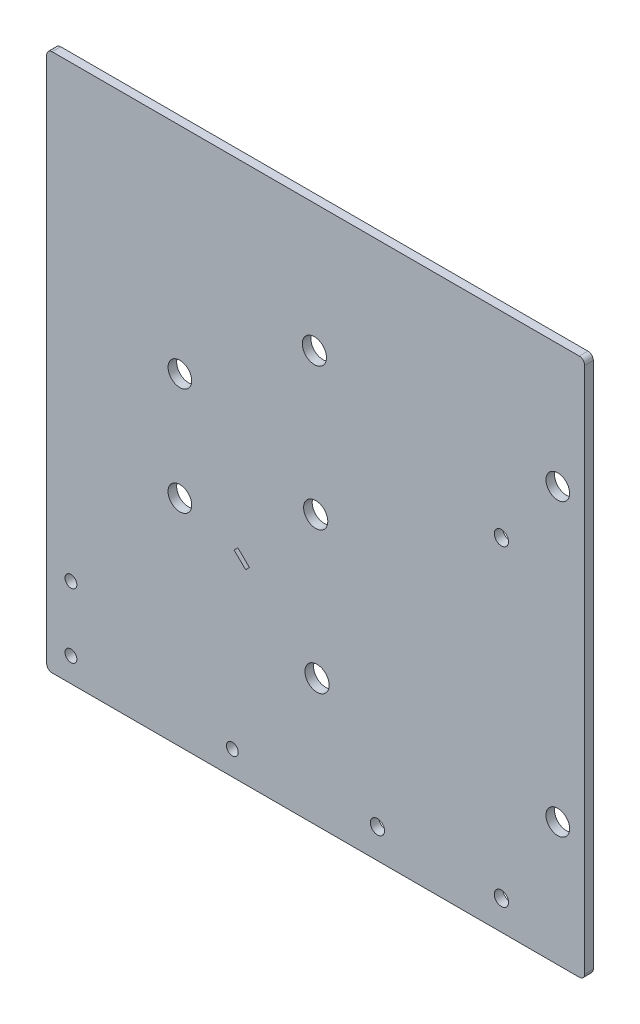
SolidWorks part; units mm, degrees
material "FR4_stuffedProtoboard"
ref_plane "Front Plane" through (0, 0, 0) normal (0, 0, 1) x (1, 0, 0)
ref_plane "Top Plane" through (0, 0, 0) normal (0, 1, 0) x (1, 0, 0)
ref_plane "Right Plane" through (0, 0, 0) normal (1, 0, 0) x (0, 0, -1)
sketch "Sketch1" plane through (0, 0, 0) normal (0, 0, 1) x (1, 0, 0)
  line L1 (-50, -50) -> (50, -50)
  line L2 (-50, -50) -> (-50, 50)
  line L3 (-50, 50) -> (50, 50)
  line L4 (50, -50) -> (50, 50)
  line L5 (-50, -50) -> (50, 50) construction
  line L6 (-50, 50) -> (50, -50) construction
  dimension "D1" = 100
extrude "Boss-Extrude1" add sketch "Sketch1" along normal blind 1.6
sketch "Sketch2" [suppressed] plane through (0, 0, 1.6) normal (0, 0, 1) x (1, 0, 0)
  circle A0 centre (0, 0) radius 50
  line M2 (50, -50) -> (50, 50)
  line M3 (50, 50) -> (-50, 50)
  line M4 (-50, 50) -> (-50, -50)
  line M5 (-50, -50) -> (50, -50)
  dimension "D1" = 100
extrude "Cut-Extrude1" [suppressed] cut sketch "Sketch2" against normal blind 1.6 contours A0 M3 M4 | A0 M4 M5 | A0 M5 M2 | A0 M2 M3
sketch "Sketch3" plane through (0, 0, 1.6) normal (0, 0, -1) x (-1, 0, 0)
  line L0 (-40, -22) -> (-50, -22) construction
  line L1 (-40, -32) -> (-40, -22) construction
  line L2 (-50, -32) -> (-40, -32) construction
  line L3 (-50, -22) -> (-50, -32) construction
  line L4 (-40, -22) -> (-50, -22)
  line L5 (-40, -32) -> (-40, -22)
  line L6 (-50, -32) -> (-40, -32)
  line L7 (-50, -22) -> (-50, -32)
  line L8 (-40, 22) -> (-40, 32) construction
  line L9 (-40, 32) -> (-50, 32) construction
  line L10 (-50, 32) -> (-50, 22) construction
  line L11 (-50, 22) -> (-40, 22) construction
  line L12 (-40, 22) -> (-40, 32)
  line L13 (-40, 32) -> (-50, 32)
  line L14 (-50, 32) -> (-50, 22)
  line L15 (-50, 22) -> (-40, 22)
  line L16 (5, -22) -> (-5, -22) construction
  line L17 (5, -32) -> (5, -22) construction
  line L18 (-5, -32) -> (5, -32) construction
  line L19 (-5, -22) -> (-5, -32) construction
  line L20 (5, -22) -> (-5, -22)
  line L21 (5, -32) -> (5, -22)
  line L22 (-5, -32) -> (5, -32)
  line L23 (-5, -22) -> (-5, -32)
  line L24 (5, 22) -> (5, 32) construction
  line L25 (5, 32) -> (-5, 32) construction
  line L26 (-5, 32) -> (-5, 22) construction
  line L27 (-5, 22) -> (5, 22) construction
  line L28 (5, 22) -> (5, 32)
  line L29 (5, 32) -> (-5, 32)
  line L30 (-5, 32) -> (-5, 22)
  line L31 (-5, 22) -> (5, 22)
  line L32 (17.2447, 25) -> (45.2447, 25) construction
  line L33 (45.2447, 25) -> (45.2447, -25) construction
  line L34 (17.2447, -25) -> (45.2447, -25) construction
  line L35 (17.2447, 25) -> (17.2447, -25) construction
  line L36 (17.2447, 25) -> (45.2447, 25)
  line L37 (45.2447, 25) -> (45.2447, -25)
  line L38 (17.2447, -25) -> (45.2447, -25)
  line L39 (17.2447, 25) -> (17.2447, -25)
  circle A0 centre (0.2447, 26.2506) radius 2.2479 construction
  circle A2 centre (0.2447, 26.2506) radius 2.2479
  circle A3 centre (0, 0) radius 2.2479
  circle A4 centre (-34.525, -44.525) radius 1.325 construction
  circle A6 centre (-34.525, -44.525) radius 1.325
  circle A8 centre (-0.2446, -26.2471) radius 2.2479 construction
  circle A9 centre (-0.2446, -26.2471) radius 2.2479
  circle A11 centre (-45, -27) radius 2.2
  circle A13 centre (-45, 27) radius 2.2
  circle A14 centre (-34.525, 13.525) radius 1.325 construction
  circle A15 centre (-34.525, 13.525) radius 1.325
  circle A16 centre (15.5, -45.5) radius 1.1 construction
  circle A17 centre (15.5, -45.5) radius 1.1
  circle A18 centre (45.5, -45.5) radius 1.1 construction
  circle A19 centre (45.5, -45.5) radius 1.1
  circle A20 centre (45.5, -33.5) radius 1.1 construction
  circle A21 centre (45.5, -33.5) radius 1.1
  circle A22 centre (-11.475, -44.525) radius 1.325 construction
  circle A23 centre (-11.475, -44.525) radius 1.325
  circle A24 centre (25.2447, -9.9994) radius 2.2 construction
  circle A25 centre (25.2447, -9.9994) radius 2.2
  circle A26 centre (25.2447, 10.0006) radius 2.2 construction
  circle A27 centre (25.2447, 10.0006) radius 2.2
  circle A28 centre (-45, 27) radius 2.2 construction
  circle A29 centre (-45, 27) radius 2.2
  circle A30 centre (-45, -27) radius 2.2 construction
  circle A31 centre (-45, -27) radius 2.2
  dimension "D1" = 4.4958
extrude "Cut-Extrude2" cut sketch "Sketch3" along normal through all contours A13 | A11 | A2 | A9 | A3 | A15 | A6 | A23 | A27 | A25 | A17 | A21 | A19 region at (-0.2447, 26.2506, 1.6) region at (0, 0, 1.6) region at (34.525, -44.525, 1.6) region at (0.2446, -26.2471, 1.6) region at (45, -27, 1.6) region at (45, 27, 1.6) region at (34.525, 13.525, 1.6) region at (-15.5, -45.5, 1.6) region at (-45.5, -45.5, 1.6) region at (-45.5, -33.5, 1.6) region at (11.475, -44.525, 1.6) region at (-25.2447, -9.9994, 1.6) region at (-25.2447, 10.0006, 1.6)
sketch "Sketch4" plane through (0, 0, 1.6) normal (0, 0, 1) x (1, 0, 0)
  line L0 (38, -44.25) -> (38, -18.925) construction
  line L5 (38, -44.25) -> (38, -18.925)
  line L6 (11.75, -48) -> (34.25, -48) construction
  line L7 (11.75, -48) -> (34.25, -48)
  line L8 (8, -44.25) -> (8, 13.25) construction
  line L9 (8, -44.25) -> (8, 13.25)
  line L11 (33, -3) -> (33, -48) construction
  line L13 (34.25, 17) -> (11.75, 17)
  line L14 (38, 13.25) -> (38, -18.925)
  line L15 (-48, -48) -> (-13, -48) construction
  line L16 (-48, -48) -> (-13, -48)
  line L17 (-48, -31) -> (-48, -48) construction
  line L18 (-48, -31) -> (-48, -48)
  line L19 (-13, -40.5) -> (-13, -32.5) construction
  line L20 (-13, -40.5) -> (-13, -32.5)
  line L21 (-13, -48) -> (-13, -40.5) construction
  line L22 (-13, -48) -> (-13, -40.5)
  line L23 (-13, -32.5) -> (-13, -31) construction
  line L24 (-13, -32.5) -> (-13, -31)
  line L25 (-13, -31) -> (-48, -31) construction
  line L26 (-13, -31) -> (-48, -31)
  line L27 (-20, -34) -> (-20, -48) construction
  arc A0 (34.25, -48) -> (38, -44.25) centre (34.25, -44.25) ccw construction
  arc A1 (34.25, -48) -> (38, -44.25) centre (34.25, -44.25) ccw
  arc A2 (8, -44.25) -> (11.75, -48) centre (11.75, -44.25) ccw construction
  arc A3 (8, -44.25) -> (11.75, -48) centre (11.75, -44.25) ccw
  arc A4 (11.75, 17) -> (8, 13.25) centre (11.75, 13.25) ccw construction
  arc A5 (11.75, 17) -> (8, 13.25) centre (11.75, 13.25) ccw
  arc A6 (38, 13.25) -> (34.25, 17) centre (34.25, 13.25) ccw construction
  arc A7 (38, 13.25) -> (34.25, 17) centre (34.25, 13.25) ccw
  text T0 "Raspberry Pi Zero W" font "Century Gothic" height 2
  text T1 "Atheros" font "Century Gothic" height 2
  dimension "D1" = 5
  dimension "D2" = 20
  dimension "D3" = 3
  dimension "D4" = 7
fillet "Fillet1" radius 1 4 edges at (-50, -50, 0.8) (-50, 50, 0.8) (50, -50, 0.8) (50, 50, 0.8)
sketch "Sketch5" plane through (0, 0, 0) normal (0, 0, -1) x (-1, 0, 0)
  line L0 (-10.2815, -30.1538) -> (-10.1686, -18.0444) construction
  line L5 (9.8305, -18.2308) -> (9.7177, -30.3402) construction
  line L6 (-10.2815, -30.1538) -> (-10.1686, -18.0444)
  line L7 (9.8305, -18.2308) -> (9.7177, -30.3402)
  line L8 (-9.8305, 18.2342) -> (-9.7176, 30.3436) construction
  line L9 (7.6991, -32.3214) -> (-8.3002, -32.1723) construction
  line L10 (-9.8305, 18.2342) -> (-9.7176, 30.3436)
  line L11 (7.6991, -32.3214) -> (-8.3002, -32.1723)
  line L12 (-7.6991, 32.3249) -> (8.3002, 32.1757) construction
  line L13 (10.2815, 30.1572) -> (10.1686, 18.0478) construction
  line L14 (-7.6991, 32.3249) -> (8.3002, 32.1757)
  line L15 (10.2815, 30.1572) -> (10.1686, 18.0478)
  line L16 (12.3214, -14.693) -> (14.4628, -12.5919)
  line L17 (14.4628, -12.5919) -> (15.1632, -13.3057)
  line L18 (15.1632, -13.3057) -> (13.0218, -15.4068)
  line L19 (13.0218, -15.4068) -> (12.3214, -14.693)
  line L20 (14.0925, -14.3562) -> (12.9198, -13.1611) construction
  arc A0 (-10.1686, -18.0444) -> (-11.0496, -16.368) centre (-12.1685, -18.0257) ccw construction
  arc A1 (10.6278, -16.6514) -> (9.8305, -18.2308) centre (11.8304, -18.2494) ccw construction
  arc A2 (16.4357, -10.9495) -> (11.0496, 16.3715) centre (0, 0.0017) ccw construction
  arc A3 (-10.7425, 16.5746) -> (-11.0496, -16.368) centre (0, 0.0017) ccw construction
  arc A4 (-10.1686, -18.0444) -> (-11.0496, -16.368) centre (-12.1685, -18.0257) ccw
  arc A5 (10.6278, -16.6514) -> (9.8305, -18.2308) centre (11.8304, -18.2494) ccw
  arc A6 (16.4357, -10.9495) -> (11.0496, 16.3715) centre (0, 0.0017) ccw
  arc A7 (-10.7425, 16.5746) -> (-11.0496, -16.368) centre (0, 0.0017) ccw
  arc A8 (-7.6991, 32.3249) -> (-9.7176, 30.3436) centre (-7.7177, 30.325) ccw construction
  arc A9 (-10.7425, 16.5746) -> (-9.8305, 18.2342) centre (-11.8304, 18.2528) ccw construction
  arc A10 (-10.2815, -30.1538) -> (-8.3002, -32.1723) centre (-8.2816, -30.1724) ccw construction
  arc A11 (-7.6991, 32.3249) -> (-9.7176, 30.3436) centre (-7.7177, 30.325) ccw
  arc A12 (-10.7425, 16.5746) -> (-9.8305, 18.2342) centre (-11.8304, 18.2528) ccw
  arc A13 (-10.2815, -30.1538) -> (-8.3002, -32.1723) centre (-8.2816, -30.1724) ccw
  arc A14 (7.6991, -32.3214) -> (9.7177, -30.3402) centre (7.7177, -30.3215) ccw construction
  arc A15 (7.6991, -32.3214) -> (9.7177, -30.3402) centre (7.7177, -30.3215) ccw
  arc A16 (10.2815, 30.1572) -> (8.3002, 32.1757) centre (8.2816, 30.1758) ccw construction
  arc A17 (10.1686, 18.0478) -> (11.0496, 16.3715) centre (12.1686, 18.0292) ccw construction
  arc A18 (10.2815, 30.1572) -> (8.3002, 32.1757) centre (8.2816, 30.1758) ccw
  arc A19 (10.1686, 18.0478) -> (11.0496, 16.3715) centre (12.1686, 18.0292) ccw
  spline S0 degree 3 poles (236.2137, 957.5717) (-572.564, -911.6818) (832.8385, 667.6942) (-927.1373, -353.6621) knots -32.672953 -32.672953 -32.672953 -32.672953 33.103808 33.103808 33.103808 33.103808 only from (10.6278, -16.6514) to (13.1907, -13.4372) construction
  spline S1 degree 3 poles (370.0588, 920.7176) (-683.0739, -819.543) (922.6586, 553.6076) (-962.4789, -215.2099) knots -32.327633 -32.327633 -32.327633 -32.327633 33.901859 33.901859 33.901859 33.901859 only from (13.1907, -13.4372) to (16.4373, -10.9505) construction
  spline S2 degree 3 poles (10.6278, -16.6514) (11.5942, -15.6755) (12.4548, -14.597) (13.1907, -13.4372) knots 0 0 0 0 1 1 1 1
  spline S3 degree 3 poles (13.1907, -13.4372) (14.3581, -12.7272) (15.4474, -11.8923) (16.4373, -10.9505) knots 0 0 0 0 1 1 1 1
  dimension "D1" = 1
  dimension "D2" = 3
extrude "Cut-Extrude4" cut sketch "Sketch5" against normal through all contours L18 L19 L16 L17
